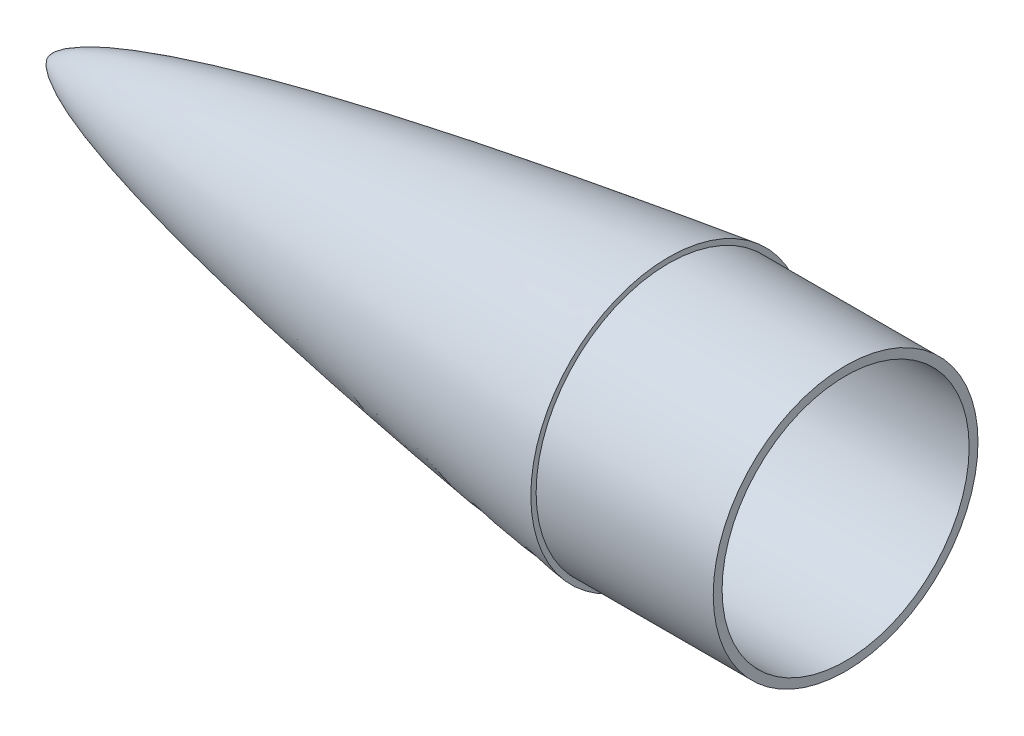
SolidWorks part; units mm, degrees
ref_plane "Front Plane" through (0, 0, 0) normal (0, 0, 1) x (1, 0, 0)
ref_plane "Top Plane" through (0, 0, 0) normal (0, 1, 0) x (1, 0, 0)
ref_plane "Right Plane" through (0, 0, 0) normal (1, 0, 0) x (0, 0, -1)
sketch "Sketch1" plane through (0, 0, 0) normal (0, 0, 1) x (1, 0, 0)
  line L0 (0, 0) -> (177.8, 0)
  line L1 (55, 0) -> (-55, 0) construction
  line L2 (177.8, 0) -> (177.8, 39.497)
  spline S0 degree 4 poles (0, 0) (0.0015, 0.042) (0.0091, 0.1255) (0.0329, 0.2406) (0.081, 0.3988) (0.1528, 0.5803) (0.2605, 0.798) (0.4311, 1.0775) (0.6931, 1.4304) (1.0922, 1.8785) (1.7171, 2.4648) (2.723, 3.2521) (4.3979, 4.3398) (7.2598, 5.8685) (12.089, 7.9709) (19.9298, 10.7503) (30.5223, 13.8323) (43.2716, 17.003) (57.3042, 20.0811) (71.3844, 22.888) (83.7511, 25.1673) (94.3499, 27.0187) (104.993, 28.8052) (113.8129, 30.2342) (122.7524, 31.6326) (131.5225, 32.9672) (138.7937, 34.0459) (147.3509, 35.2967) (156.8321, 36.6374) (164.7754, 37.743) (175.5263, 39.1962) (180.67, 39.8804) (187.7683, 40.8142) (191.3844, 41.2802) (194.1269, 41.6359) (194.8908, 41.7324) (195.6141, 41.8261) knots 0 0 0 0 0 0.000831 0.001663 0.002324 0.003277 0.004699 0.006471 0.008811 0.011983 0.016585 0.023443 0.034114 0.051543 0.080868 0.127798 0.199007 0.270216 0.341424 0.412633 0.483841 0.519446 0.55505 0.626258 0.661863 0.697467 0.733071 0.768676 0.839884 0.875488 0.911093 0.955546 0.977773 0.988887 1 1 1 1 1 construction
  spline S1 degree 4 poles (0, 0) (0.0015, 0.042) (0.0091, 0.1255) (0.0329, 0.2406) (0.081, 0.3988) (0.1528, 0.5803) (0.2605, 0.798) (0.4311, 1.0775) (0.6931, 1.4304) (1.0922, 1.8785) (1.7171, 2.4648) (2.723, 3.2521) (4.3979, 4.3398) (7.2598, 5.8685) (12.089, 7.9709) (19.9298, 10.7503) (30.5223, 13.8323) (43.2716, 17.003) (57.3042, 20.0811) (71.3844, 22.888) (83.7511, 25.1673) (94.3499, 27.0187) (104.993, 28.8052) (113.8129, 30.2342) (122.7524, 31.6326) (131.5225, 32.9672) (138.7937, 34.0459) (147.3509, 35.2967) (156.8321, 36.6374) (164.7754, 37.743) (172.9688, 38.8505) (176.1787, 39.2809) (177.8, 39.497) knots 0 0 0 0 0 0.000831 0.001663 0.002324 0.003277 0.004699 0.006471 0.008811 0.011983 0.016585 0.023443 0.034114 0.051543 0.080868 0.127798 0.199007 0.270216 0.341424 0.412633 0.483841 0.519446 0.55505 0.626258 0.661863 0.697467 0.733071 0.768676 0.839884 0.875488 0.911093 0.911093 0.911093 0.911093 0.911093
revolve "Revolve1" add sketch "Sketch1" angle 360 about L0
sketch "Sketch2" plane through (177.8, 0, 0) normal (1, 0, 0) x (0, 0, -1)
  circle A0 centre (0, 0) radius 37.973
  dimension "D1" = 75.946
extrude "Boss-Extrude1" add sketch "Sketch2" along normal blind 50.8
shell "Shell3" thickness 2.54 removed face at (228.6, 0, -37.973)
